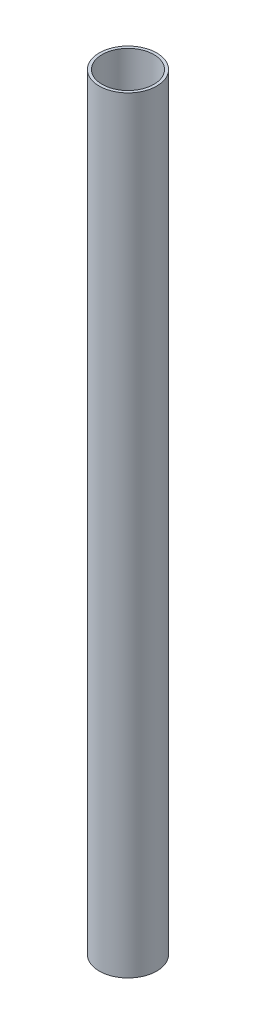
SolidWorks part; units mm, degrees
ref_plane "Front Plane" through (0, 0, 0) normal (0, 0, 1) x (1, 0, 0)
ref_plane "Top Plane" through (0, 0, 0) normal (0, 1, 0) x (1, 0, 0)
ref_plane "Right Plane" through (0, 0, 0) normal (1, 0, 0) x (0, 0, -1)
sketch "Sketch1" plane through (0, 0, 0) normal (0, 1, 0) x (1, 0, 0)
  circle A0 centre (0, 0) radius 15
  circle A1 centre (0, 0) radius 13.5
  dimension "D1" = 1.5
  dimension "D2" = 30
extrude "Boss-Extrude1" add sketch "Sketch1" along normal blind 400
ref_plane "Plane1" through (0, 0, 30) normal (0, 0, 1) x (1, 0, 0)
